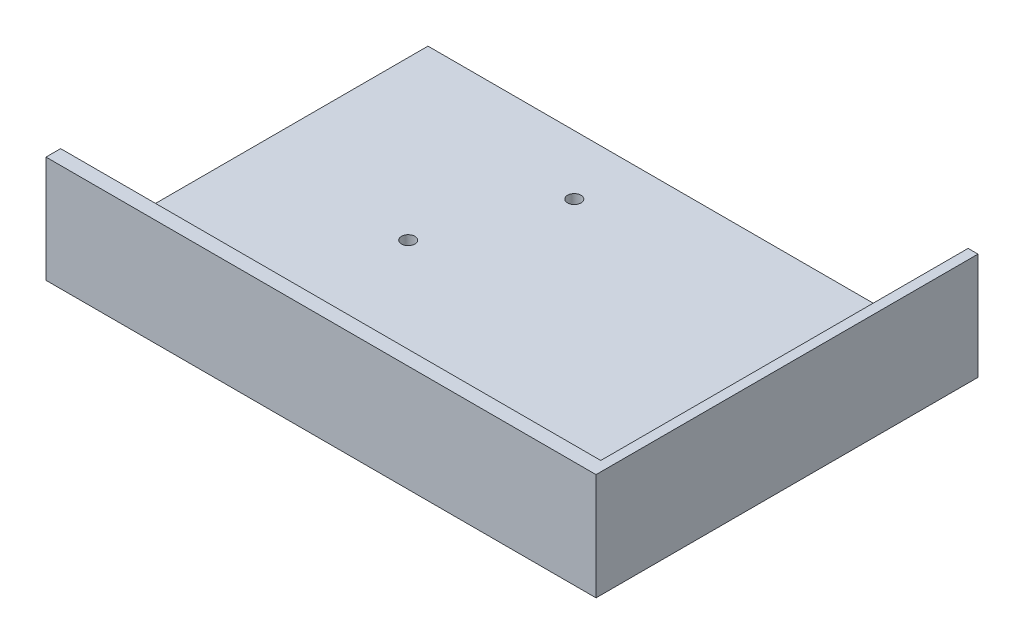
SolidWorks part; units mm, degrees
ref_plane "Front Plane" through (0, 0, 0) normal (0, 0, 1) x (1, 0, 0)
ref_plane "Top Plane" through (0, 0, 0) normal (0, 1, 0) x (1, 0, 0)
ref_plane "Right Plane" through (0, 0, 0) normal (1, 0, 0) x (0, 0, -1)
sketch "Sketch1" plane through (0, 0, 0) normal (0, 1, 0) x (1, 0, 0)
  line L1 (-139.1, -96.6) -> (139.1, -96.6)
  line L2 (-139.1, -96.6) -> (-139.1, 96.6)
  line L3 (-139.1, 96.6) -> (139.1, 96.6)
  line L4 (139.1, -96.6) -> (139.1, 96.6)
  line L5 (-139.1, -96.6) -> (139.1, 96.6) construction
  line L6 (-139.1, 96.6) -> (139.1, -96.6) construction
  dimension "D1" = 278.2
  dimension "D2" = 193.2
extrude "Shell Block" add sketch "Sketch1" along normal blind 27
ref_plane "Shell Front" through (0, 27, 0) normal (0, 1, 0) x (1, 0, 0)
sketch "Sketch2" plane through (0, 27, 0) normal (0, 1, 0) x (1, 0, 0)
  line L1 (-136.6, -92.9) -> (136.6, -92.9)
  line L2 (-136.6, -92.9) -> (-136.6, 92.9)
  line L3 (-136.6, 92.9) -> (136.6, 92.9)
  line L4 (136.6, -92.9) -> (136.6, 92.9)
  line L5 (-136.6, -92.9) -> (136.6, 92.9) construction
  line L6 (-136.6, 92.9) -> (136.6, -92.9) construction
  dimension "D1" = 273.2
  dimension "D2" = 185.8
extrude "Front Opening" cut sketch "Sketch2" against normal blind 1.5
ref_plane "Under Lip" through (0, 25.5, 0) normal (0, 1, 0) x (1, 0, 0)
sketch "Sketch3" plane through (0, 25.5, 0) normal (0, 1, 0) x (1, 0, 0)
  line L1 (-136.6, -94.1) -> (136.6, -94.1)
  line L2 (-136.6, -94.1) -> (-136.6, 94.1)
  line L3 (-136.6, 94.1) -> (136.6, 94.1)
  line L4 (136.6, -94.1) -> (136.6, 94.1)
  line L5 (-136.6, -94.1) -> (136.6, 94.1) construction
  line L6 (-136.6, 94.1) -> (136.6, -94.1) construction
  dimension "D1" = 273.2
  dimension "D2" = 188.2
extrude "Display Pocket" cut sketch "Sketch3" against normal blind 22.5
ref_plane "Back Inner" through (0, 3, 0) normal (0, 1, 0) x (1, 0, 0)
sketch "Sketch4" plane through (0, 3, 0) normal (0, 1, 0) x (1, 0, 0)
  line L1 (-69, 28) -> (-66, 28)
  line L2 (-69, 28) -> (-69, 84)
  line L3 (-69, 84) -> (-66, 84)
  line L4 (-66, 28) -> (-66, 84)
  line L6 (-69, -84) -> (-66, -84)
  line L7 (-69, -84) -> (-69, -28)
  line L8 (-69, -28) -> (-66, -28)
  line L9 (-66, -84) -> (-66, -28)
  line L11 (-77, 28) -> (-74, 28)
  line L12 (-77, 28) -> (-77, 84)
  line L13 (-77, 84) -> (-74, 84)
  line L14 (-74, 28) -> (-74, 84)
  line L16 (-77, -84) -> (-74, -84)
  line L17 (-77, -84) -> (-77, -28)
  line L18 (-77, -28) -> (-74, -28)
  line L19 (-74, -84) -> (-74, -28)
  line L21 (-85, 28) -> (-82, 28)
  line L22 (-85, 28) -> (-85, 84)
  line L23 (-85, 84) -> (-82, 84)
  line L24 (-82, 28) -> (-82, 84)
  line L26 (-85, -84) -> (-82, -84)
  line L27 (-85, -84) -> (-85, -28)
  line L28 (-85, -28) -> (-82, -28)
  line L29 (-82, -84) -> (-82, -28)
  line L31 (-93, 28) -> (-90, 28)
  line L32 (-93, 28) -> (-93, 84)
  line L33 (-93, 84) -> (-90, 84)
  line L34 (-90, 28) -> (-90, 84)
  line L36 (-93, -84) -> (-90, -84)
  line L37 (-93, -84) -> (-93, -28)
  line L38 (-93, -28) -> (-90, -28)
  line L39 (-90, -84) -> (-90, -28)
  line L41 (-101, 28) -> (-98, 28)
  line L42 (-101, 28) -> (-101, 84)
  line L43 (-101, 84) -> (-98, 84)
  line L44 (-98, 28) -> (-98, 84)
  line L46 (-101, -84) -> (-98, -84)
  line L47 (-101, -84) -> (-101, -28)
  line L48 (-101, -28) -> (-98, -28)
  line L49 (-98, -84) -> (-98, -28)
  line L51 (-109, 28) -> (-106, 28)
  line L52 (-109, 28) -> (-109, 84)
  line L53 (-109, 84) -> (-106, 84)
  line L54 (-106, 28) -> (-106, 84)
  line L56 (-109, -84) -> (-106, -84)
  line L57 (-109, -84) -> (-109, -28)
  line L58 (-109, -28) -> (-106, -28)
  line L59 (-106, -84) -> (-106, -28)
  line L61 (-117, 28) -> (-114, 28)
  line L62 (-117, 28) -> (-117, 84)
  line L63 (-117, 84) -> (-114, 84)
  line L64 (-114, 28) -> (-114, 84)
  line L66 (-117, -84) -> (-114, -84)
  line L67 (-117, -84) -> (-117, -28)
  line L68 (-117, -28) -> (-114, -28)
  line L69 (-114, -84) -> (-114, -28)
  line L71 (-125, 28) -> (-122, 28)
  line L72 (-125, 28) -> (-125, 84)
  line L73 (-125, 84) -> (-122, 84)
  line L74 (-122, 28) -> (-122, 84)
  line L76 (-125, -84) -> (-122, -84)
  line L77 (-125, -84) -> (-125, -28)
  line L78 (-125, -28) -> (-122, -28)
  line L79 (-122, -84) -> (-122, -28)
extrude "Vent Slots" cut sketch "Sketch4" against normal blind 4
sketch "Sketch5" plane through (0, 0, 0) normal (1, 0, 0) x (0, 0, -1)
  line L1 (-29, 5) -> (29, 5)
  line L2 (-29, 5) -> (-29, 21)
  line L3 (-29, 21) -> (29, 21)
  line L4 (29, 5) -> (29, 21)
extrude "Cable Exit (-X short side)" cut sketch "Sketch5" against normal blind 140.1
sketch "Sketch6" plane through (0, 3, 0) normal (0, 1, 0) x (1, 0, 0)
  circle A0 centre (-40, -45) radius 1.7
  circle A1 centre (-40, 45) radius 1.7
  circle A2 centre (40, -45) radius 1.7
  circle A3 centre (40, 45) radius 1.7
  circle A4 centre (-52, -15) radius 1.7
  circle A5 centre (-52, 15) radius 1.7
  circle A6 centre (52, -15) radius 1.7
  circle A7 centre (52, 15) radius 1.7
  circle A8 centre (-12, -82) radius 1.7
  circle A9 centre (-12, 82) radius 1.7
  circle A10 centre (12, -82) radius 1.7
  circle A11 centre (12, 82) radius 1.7
  circle A12 centre (-124, -12) radius 1.7
  circle A13 centre (-124, 12) radius 1.7
  circle A14 centre (124, -12) radius 1.7
  circle A15 centre (124, 12) radius 1.7
extrude "Bolt Holes" cut sketch "Sketch6" against normal blind 4
sketch "Sketch7" plane through (0, 0, 0) normal (0, 1, 0) x (1, 0, 0)
  line L1 (-200, -200) -> (0, -200)
  line L2 (-200, -200) -> (-200, 200)
  line L3 (-200, 200) -> (0, 200)
  line L4 (0, -200) -> (0, 200)
extrude "Keep one half (X)" cut sketch "Sketch7" against normal through all and the other way through all
sketch "Sketch8" plane through (0, 0, 0) normal (0, 1, 0) x (1, 0, 0)
  line L1 (-200, 0) -> (200, 0)
  line L2 (-200, 0) -> (-200, 200)
  line L3 (-200, 200) -> (200, 200)
  line L4 (200, 0) -> (200, 200)
extrude "Keep one quarter (Z)" cut sketch "Sketch8" against normal through all and the other way through all
equation "\"DispL\"= 272.0"
equation "\"DispW\"= 187.0"
equation "\"DispT\"= 20.0"
equation "\"Clr\"= 0.6"
equation "\"Wall\"= 2.5"
equation "\"BackT\"= 3.0"
equation "\"CableRoom\"= 4.0"
equation "\"LipW\"= 1.2"
equation "\"LipT\"= 1.5"
equation "\"CableW\"= 58.0"
equation "\"CableH\"= 16.0"
equation "\"BoltD\"= 3.4"
equation "\"ShellL\"= \"DispL\" + 2 * \"Clr\" + 2 * \"Wall\""
equation "\"ShellW\"= \"DispW\" + 2 * \"Clr\" + 2 * \"Wall\""
equation "\"ShellH\"= \"BackT\" + \"DispT\" + \"CableRoom\""
equation "\"D1@Sketch1\" = \"ShellL\""
equation "\"D2@Sketch1\" = \"ShellW\""
equation "\"D1@Shell Block\" = \"ShellH\""
equation "\"D1@Shell Front\" = \"ShellH\""
equation "\"D1@Sketch2\" = \"DispL\" + 2 * \"Clr\""
equation "\"D2@Sketch2\" = \"DispW\" + 2 * \"Clr\" - 2 * \"LipW\""
equation "\"D1@Front Opening\" = \"LipT\""
equation "\"D1@Under Lip\" = \"ShellH\" - \"LipT\""
equation "\"D1@Sketch3\" = \"DispL\" + 2 * \"Clr\""
equation "\"D2@Sketch3\" = \"DispW\" + 2 * \"Clr\""
equation "\"D1@Display Pocket\" = \"ShellH\" - \"LipT\" - \"BackT\""
equation "\"D1@Back Inner\" = \"BackT\""
